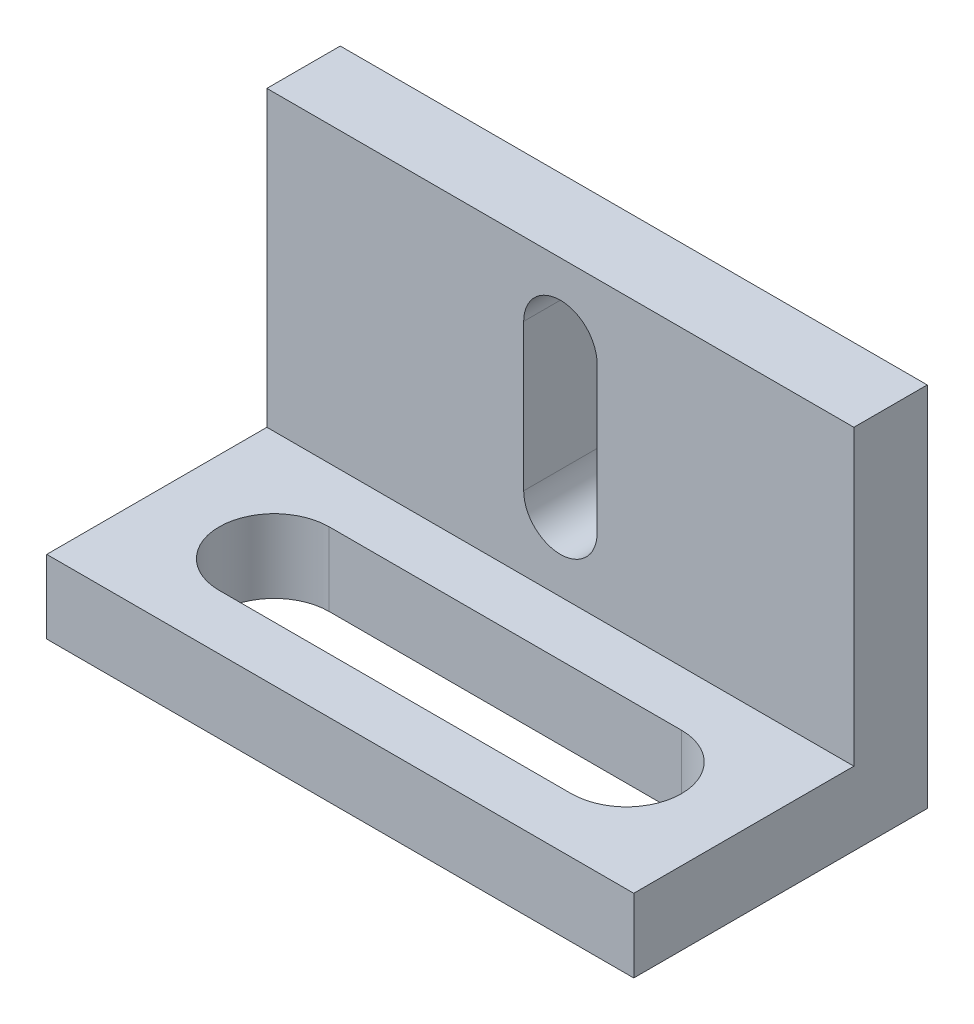
SolidWorks part; units mm, degrees
material "6061 Alloy"
ref_plane "Front Plane" through (0, 0, 0) normal (0, 0, 1) x (1, 0, 0)
ref_plane "Top Plane" through (0, 0, 0) normal (0, 1, 0) x (1, 0, 0)
ref_plane "Right Plane" through (0, 0, 0) normal (1, 0, 0) x (0, 0, -1)
sketch "Sketch1" plane through (0, 0, 0) normal (0, 1, 0) x (1, 0, 0)
  line L1 (12.7, -6.35) -> (-12.7, -6.35)
  line L2 (12.7, -6.35) -> (12.7, 6.35)
  line L3 (12.7, 6.35) -> (-12.7, 6.35)
  line L4 (-12.7, -6.35) -> (-12.7, 6.35)
  line L5 (12.7, -6.35) -> (-12.7, 6.35) construction
  line L6 (12.7, 6.35) -> (-12.7, -6.35) construction
  point P0 (0, 0)
  dimension "D1" = 25.4
  dimension "D2" = 12.7
extrude "Boss-Extrude1" add sketch "Sketch1" along normal blind 3.175
sketch "Sketch2" plane through (0, 3.175, 0) normal (0, 1, 0) x (1, 0, 0)
  line L0 (12.7, -6.35) -> (12.7, 6.35) construction
  line L1 (-12.7, 6.35) -> (12.7, 6.35)
  line L2 (-12.7, 6.35) -> (-12.7, 3.175)
  line L3 (-12.7, 3.175) -> (12.7, 3.175)
  line L4 (12.7, 6.35) -> (12.7, 3.175)
  dimension "D1" = 3.175
extrude "Boss-Extrude2" add sketch "Sketch2" along normal blind 12.7
sketch "Sketch3" plane through (0, 0, -3.175) normal (0, 0, 1) x (1, 0, 0)
  line L0 (0, 12.7) -> (0, 6.35) construction
  line L1 (1.5875, 12.7) -> (1.5875, 6.35)
  line L2 (-1.5875, 12.7) -> (-1.5875, 6.35)
  line L3 (-12.7, 15.875) -> (12.7, 15.875) construction
  arc A0 (1.5875, 12.7) -> (-1.5875, 12.7) centre (0, 12.7) ccw
  arc A1 (-1.5875, 6.35) -> (1.5875, 6.35) centre (0, 6.35) ccw
  point P3 (0, 9.525)
  dimension "D1" = 3.175
  dimension "D2" = 6.35
  dimension "D3" = 3.175
extrude "Cut-Extrude1" cut sketch "Sketch3" against normal through all
sketch "Sketch4" plane through (0, 3.175, 0) normal (0, 1, 0) x (1, 0, 0)
  line L0 (-7.62, -1.5875) -> (7.62, -1.5875) construction
  line L1 (-7.62, 0.7937) -> (7.62, 0.7938)
  line L2 (-7.62, -3.9688) -> (7.62, -3.9687)
  line L4 (-12.7, -6.35) -> (12.7, -6.35) construction
  arc A0 (-7.62, 0.7937) -> (-7.62, -3.9688) centre (-7.62, -1.5875) ccw
  arc A1 (7.62, -3.9687) -> (7.62, 0.7938) centre (7.62, -1.5875) ccw
  point P2 (0, -1.5875)
  dimension "D1" = 4.7625
  dimension "D2" = 4.7625
  dimension "D3" = 4.7625
  dimension "D4" = 15.24
  dimension "D5" = 0
extrude "Cut-Extrude2" cut sketch "Sketch4" against normal through all
